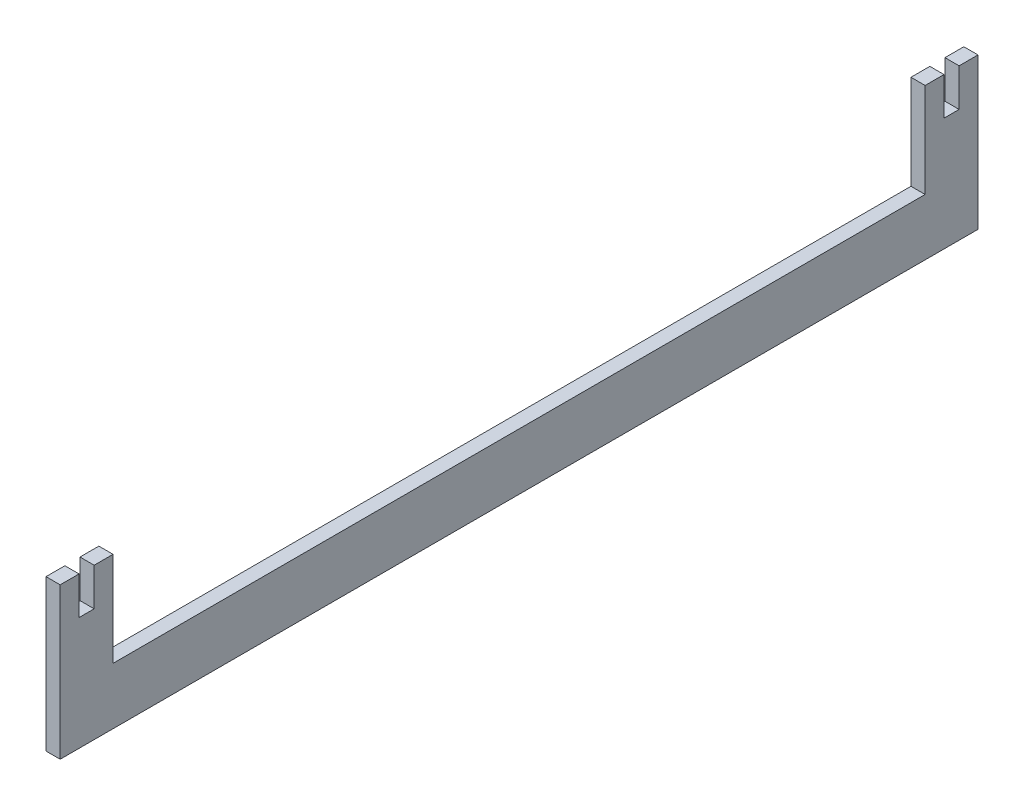
SolidWorks part; units mm, degrees
ref_plane "Front Plane" through (0, 0, 0) normal (0, 0, 1) x (1, 0, 0)
ref_plane "Top Plane" through (0, 0, 0) normal (0, 1, 0) x (1, 0, 0)
ref_plane "Right Plane" through (0, 0, 0) normal (1, 0, 0) x (0, 0, -1)
sketch "Sketch1" plane through (0, 0, 0) normal (1, 0, 0) x (0, 0, -1)
  line L0 (-97.2, 32) -> (-97.2, 0)
  line L1 (-97.2, 0) -> (97.2, 0)
  line L2 (97.2, 0) -> (97.2, 32)
  line L3 (97.2, 32) -> (93.2, 32)
  line L4 (93.2, 32) -> (93.2, 24)
  line L5 (93.2, 24) -> (90, 24)
  line L6 (90, 24) -> (90, 32)
  line L7 (90, 32) -> (86, 32)
  line L8 (-90, 32) -> (-90, 24)
  line L9 (-90, 24) -> (-93.2, 24)
  line L10 (-93.2, 24) -> (-93.2, 32)
  line L11 (-93.2, 32) -> (-97.2, 32)
  line L12 (-86, 32) -> (-86, 12)
  line L13 (-86, 12) -> (86, 12)
  line L14 (86, 12) -> (86, 32)
  line L15 (-86, 32) -> (-90, 32)
  point P17 (0, 0)
  point P18 (0, 0)
  point P20 (0, 0)
  dimension "D2" = 8
  dimension "D3" = 4
  dimension "D4" = 3.2
  dimension "D5" = 180
  dimension "D1" = 12
  dimension "D6" = 12
extrude "Boss-Extrude1" add sketch "Sketch1" along normal blind 3
equation "\"mdfWidth\"= 3"
equation "\"cellSide\"= 180"
equation "\"mazeHeight\" = 50"
equation "\"slitHeight\"= 10"
equation "\"gripWidth\"= 6"
equation "\"wallThickness\"= 1.5"
equation "\"slitWidth\" = \"wallThickness\""
equation "\"play\"= 0.2"
equation "\"D4@Sketch1\"= \"mdfWidth\" + \"play\""
equation "\"D5@Sketch1\"= \"cellSide\""
equation "\"D1@Boss-Extrude1\"= \"mdfWidth\""
